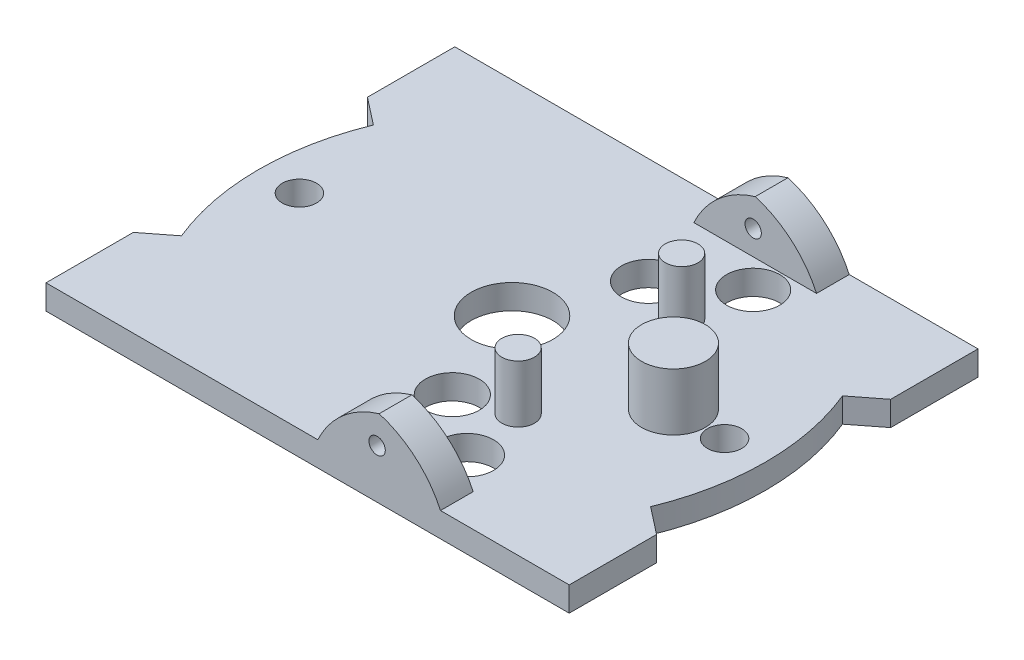
SolidWorks part; units mm, degrees
ref_plane "Front Plane" through (0, 0, 0) normal (0, 0, 1) x (1, 0, 0)
ref_plane "Top Plane" through (0, 0, 0) normal (0, 1, 0) x (1, 0, 0)
ref_plane "Right Plane" through (0, 0, 0) normal (1, 0, 0) x (0, 0, -1)
sketch "Sketch1" plane through (0, 0, 0) normal (0, 1, 0) x (1, 0, 0)
  line L0 (-32, 25) -> (32, -25) construction
  line L1 (32, -25) -> (-32, -25)
  line L2 (32, -25) -> (32, 25)
  line L3 (32, 25) -> (-32, 25)
  line L4 (-32, -25) -> (-32, 25)
  line L5 (0, 25) -> (0, -25) construction
  line L6 (32, 0) -> (-32, 0) construction
  line L7 (-32, -25) -> (32, 25) construction
  line L8 (-18.3303, 25) -> (-11.2626, 19.4783)
  line L9 (-28.6924, 11.7365) -> (-21.6247, 6.2148)
  line L10 (-32, -25) -> (-17.7305, -13.852)
  line L11 (18.3303, 25) -> (11.2626, 19.4783)
  line L12 (-11.2626, -19.4783) -> (-18.3303, -25)
  line L13 (-28.6924, 11.7365) -> (-32, 14.3205)
  line L14 (-21.6247, -6.2148) -> (-32, -14.3205)
  line L15 (28.6924, 11.7365) -> (21.6247, 6.2148)
  line L16 (21.6247, -6.2148) -> (32, -14.3205)
  line L17 (11.2626, -19.4783) -> (18.3303, -25)
  line L18 (28.6924, 11.7365) -> (32, 14.3205)
  line L19 (15.2315, 27) -> (15.2315, 25)
  line L20 (34, -27) -> (-34, -27)
  line L21 (34, -27) -> (34, 27)
  line L22 (34, 27) -> (-34, 27)
  line L23 (-34, -27) -> (-34, 27)
  line L24 (0, 27) -> (0, -27) construction
  line L25 (34, 0) -> (-34, 0) construction
  line L26 (15.2315, 25) -> (32, 25)
  line L27 (32, 14.3205) -> (34, 14.3205)
  line L28 (34, 14.3205) -> (34, 27)
  line L29 (-32, 14.3205) -> (-34, 14.3205)
  line L30 (-15.2315, 27) -> (-15.2315, 25)
  line L31 (32, -14.3205) -> (34, -14.3205)
  line L32 (15.2315, -27) -> (15.2315, -25)
  line L33 (-15.2315, -27) -> (-15.2315, -25)
  line L34 (-32, -14.3205) -> (-34, -14.3205)
  circle A0 centre (0, 0) radius 22.5
  arc A1 (-18.3303, 25) -> (-18.3303, -25) centre (0, 0) ccw
  circle A2 centre (-26, 0) radius 2.1
  circle A3 centre (26, 0) radius 2.1
  arc A4 (18.3303, -25) -> (18.3303, 25) centre (0, 0) ccw
  circle A5 centre (0, 0) radius 5
  point P33 (15.2315, 27)
  dimension "D1" = 45
  dimension "D2" = 62
  dimension "D5" = 4.2
  dimension "D9" = 10
  dimension "D3" = 64
  dimension "D4" = 50
  dimension "D6" = 26
  dimension "D7" = 68
  dimension "D8" = 54
extrude "Boss-Extrude2" add sketch "Sketch1" along normal blind 3 contours A1 L3 L4 L13 | L8 A1 L9 A0 | A0 L11 L3 L8 | L15 A4 L11 A0 | A4 L18 L2 L3 | L16 A4 L15 A0 A3 | L14 A1 L10 A0 | L9 A1 L14 A0 A2 | A1 L14 L4 L10 | A1 L10 L1 | L10 A1 L12 A0 | A0 L12 L1 L17 | L17 A4 L16 A0 | A4 L1 L2 L16 | A0 region at (27.5253, 0, 20.1834) region at (0, 0, 23.1509) region at (20.7114, 0, 16.1808) region at (25.3141, 0, 8.7765) region at (27.5253, 0, -20.1834) region at (-18.0979, 0, 19.5261) region at (20.7114, 0, -16.1808) region at (-25.0676, 0, 23.0669) region at (-23.325, 0, 12.8355) region at (0, 0, -23.1509) region at (-29.2139, 0, 18.2023) region at (-25.3141, 0, 8.7765) region at (-20.7114, 0, -16.1808) region at (-27.5253, 0, -20.1834)
extrude "Cut-Extrude2" cut sketch "Sketch1<14>" along normal blind 10 contours A5
sketch "Sketch1<14>" plane through (0, 0, 0) normal (0, 1, 0) x (1, 0, 0) same geometry as "Sketch1"
sketch "Sketch2" plane through (0, 3, 0) normal (0, 1, 0) x (1, 0, 0)
  line L0 (-26, 0) -> (26, 0) construction
  line L1 (8, 0) -> (8, 11.2082) construction
  line L2 (8.75, 0) -> (8.75, 11.2082) construction
  line L3 (8, 11.2082) -> (8, 12) construction
  line L4 (8, 12) -> (4.7, 12) construction
  line L5 (8.75, 11.2082) -> (8.75, 23) construction
  line L6 (8, 0) -> (8, -21.7165) construction
  line L7 (8.75, 0) -> (8.75, -22.7195)
  line L8 (16.25, -21) -> (16.25, -25)
  line L9 (16.25, 21) -> (1.25, 21)
  line L10 (-32, -25) -> (32, -25)
  line L11 (32, -25) -> (32, -14.3205)
  line L12 (32, -14.3205) -> (28.6924, -11.7365)
  line L13 (28.6924, 11.7365) -> (32, 14.3205)
  line L14 (32, 14.3205) -> (32, 25)
  line L15 (32, 25) -> (-32, 25)
  line L16 (-32, 25) -> (-32, 14.3205)
  line L17 (-32, 14.3205) -> (-28.6924, 11.7365)
  line L18 (-28.6924, -11.7365) -> (-32, -14.3205)
  line L19 (-32, -14.3205) -> (-32, -25)
  line L20 (-32, -25) -> (32, -25)
  line L21 (32, -25) -> (32, -14.3205)
  line L22 (32, -14.3205) -> (28.6924, -11.7365)
  line L23 (28.6924, 11.7365) -> (32, 14.3205)
  line L24 (32, 14.3205) -> (32, 25)
  line L25 (32, 25) -> (-32, 25)
  line L26 (-32, 25) -> (-32, 14.3205)
  line L27 (-32, 14.3205) -> (-28.6924, 11.7365)
  line L28 (-28.6924, -11.7365) -> (-32, -14.3205)
  line L29 (-32, -14.3205) -> (-32, -25)
  line L30 (16.25, 21) -> (16.25, 25)
  line L31 (16.25, 25) -> (1.25, 25)
  line L32 (1.25, 21) -> (1.25, 25)
  line L33 (8.75, 25) -> (8.75, 21) construction
  line L34 (16.25, 23) -> (1.25, 23) construction
  line L35 (16.25, -21) -> (1.25, -21)
  line L36 (1.25, -21) -> (1.25, -25)
  line L37 (8.75, -25) -> (8.75, -21) construction
  circle A0 centre (-26, 0) radius 2.1 construction
  circle A1 centre (-26, 0) radius 2.1
  arc A2 (28.6924, -11.7365) -> (28.6924, 11.7365) centre (0, 0) ccw
  arc A3 (-28.6924, 11.7365) -> (-28.6924, -11.7365) centre (0, 0) ccw
  arc A4 (28.6924, -11.7365) -> (28.6924, 11.7365) centre (0, 0) ccw
  arc A5 (-28.6924, 11.7365) -> (-28.6924, -11.7365) centre (0, 0) ccw
  circle A6 centre (0, 0) radius 5 construction
  circle A7 centre (0, 0) radius 5
  circle A8 centre (26, 0) radius 2.1 construction
  circle A9 centre (26, 0) radius 2.1
  circle A10 centre (0, 0) radius 8
  circle A11 centre (0, 0) radius 3
  circle A12 centre (19.75, 0) radius 11
  circle A13 centre (19.75, 0) radius 3.9
  circle A14 centre (4.7, 12) radius 3.3
  circle A15 centre (4.7, 12) radius 4.5
  circle A16 centre (12, 17.5) radius 4.5
  circle A17 centre (12, 17.5) radius 3.25
  circle A18 centre (4.7, -12) radius 3.3
  circle A19 centre (4.7, -12) radius 4.5
  circle A20 centre (12, -17.5) radius 4.5
  circle A21 centre (12, -17.5) radius 3.25
  circle A22 centre (10.75, 10) radius 2
  circle A23 centre (10.75, -10) radius 2
  point P25 (8, 0)
  point P37 (4.8326, 10.9333)
  point P39 (5.5371, 12)
  dimension "D2" = 16
  dimension "D3" = 6
  dimension "D5" = 22
  dimension "D7" = 7.8
  dimension "D8" = 6.6
  dimension "D9" = 9
  dimension "D11" = 6.5
  dimension "D13" = 9
  dimension "D6" = 4
  dimension "D4" = 0.75
  dimension "D10" = 12
  dimension "D12" = 17.5
  dimension "D14" = 15
  dimension "D15" = 4
  dimension "D16" = 10
  dimension "D1" = 0
extrude "Boss-Extrude3" add sketch "Sketch2" along normal blind 7 contours L35 L36 L20 L8 | L32 L9 L30 L25 | A15 A22 | A23 A19 | L9 A16 | A20 L35 | A23 A19 | A15 A22 | A13 region at (10.7649, 3, 9.9951) region at (8.9165, 3, 10.6061) region at (12, 3, 21.4041) region at (8.5263, 3, 23.1098) region at (8.5263, 3, -23.1098) region at (12, 3, -21.4041) region at (8.9165, 3, -10.6061) region at (10.7649, 3, -9.9951)
extrude "Cut-Extrude3" cut sketch "Sketch2<4>" against normal blind 7 contours A17 | A14 | A21 | A18 region at (12, 3, 17.5) region at (4.7, 3, -12) region at (12, 3, -17.5) region at (4.7, 3, 12)
sketch "Sketch2<4>" plane through (0, 3, 0) normal (0, 1, 0) x (1, 0, 0) same geometry as "Sketch2"
sketch "Sketch3" plane through (0, 0, 25) normal (0, 0, 1) x (1, 0, 0)
  line L0 (8.9, 11) -> (8.9, 0) construction
  line L1 (8.1251, 0) -> (8.1251, 6) construction
  line L8 (-32, 0) -> (32, 0)
  line L9 (32, 0) -> (32, 3)
  line L10 (32, 3) -> (16.25, 3)
  line L13 (16.25, 3) -> (16.25, 10)
  line L14 (16.25, 3) -> (16.25, 10)
  line L15 (-32, 3) -> (-32, 0)
  line L16 (-32, 0) -> (32, 0)
  line L17 (32, 0) -> (32, 3)
  line L18 (32, 3) -> (16.25, 3)
  line L23 (-32, 3) -> (-32, 0)
  line L24 (16.25, 10) -> (1.25, 10)
  line L25 (16.25, 10) -> (1.25, 10)
  line L26 (1.25, 10) -> (1.25, 3)
  line L27 (1.25, 10) -> (1.25, 3)
  line L28 (1.25, 3) -> (-32, 3)
  line L29 (1.25, 3) -> (-32, 3)
  circle A0 centre (8.5, 6) radius 1
  dimension "D2" = 2
  dimension "D3" = 0.4
  dimension "D4" = 6
  dimension "D1" = 0
extrude "Cut-Extrude4" cut sketch "Sketch3" against normal blind 7 and the other way through all contours A0 region at (8.5, 6, 25)
fillet "Fillet1" radius 12 4 edges at (1.25, 10, -23) (16.25, 10, -23) (1.25, 10, 23) (16.25, 10, 23)
extrude "Cut-Extrude5" cut sketch "Sketch3<3>" along normal blind 9 from surface contours A0 starting at face at (3.75, 3.3042, -25)
sketch "Sketch3<3>" plane through (0, 0, 25) normal (0, 0, 1) x (1, 0, 0) same geometry as "Sketch3"
